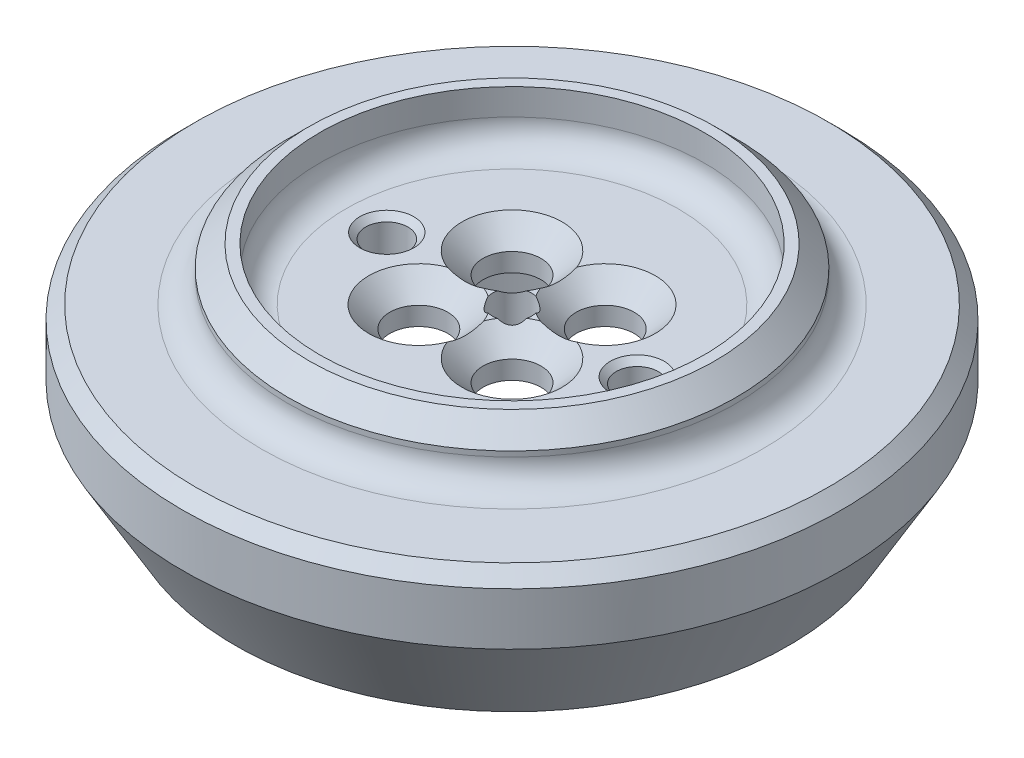
SolidWorks part; units mm, degrees
material "Brass"
ref_plane "Front Plane" through (0, 0, 0) normal (0, 0, 1) x (1, 0, 0)
ref_plane "Top Plane" through (0, 0, 0) normal (0, 1, 0) x (1, 0, 0)
ref_plane "Right Plane" through (0, 0, 0) normal (1, 0, 0) x (0, 0, -1)
sketch "Sketch1" plane through (0, 0, 0) normal (0, 1, 0) x (1, 0, 0)
  circle A0 centre (0, 0) radius 12.5
  dimension "D1" = 25
extrude "Boss-Extrude1" add sketch "Sketch1" along normal blind 1.5
sketch "Sketch2" plane through (0, 1.5, 0) normal (0, 1, 0) x (1, 0, 0)
  circle A0 centre (0, 0) radius 0.75
  dimension "D1" = 1.5
extrude "Cut-Extrude1" cut sketch "Sketch2" against normal through all both and the other way through all
hole_wizard "CSK for M2 Flat Head Machine Screw1" positions "Sketch3" profile "Sketch4" countersink size "M2" standard "ANSI Metric"
sketch "Sketch3" plane through (0, 1.5, 0) normal (0, 1, 0) x (1, 0, 0)
  line L1 (-1.7678, 1.7678) -> (1.7678, 1.7678)
  line L2 (-1.7678, 1.7678) -> (-1.7678, -1.7678)
  line L3 (-1.7678, -1.7678) -> (1.7678, -1.7678)
  line L4 (1.7678, 1.7678) -> (1.7678, -1.7678)
  line L5 (-1.7678, 1.7678) -> (1.7678, -1.7678) construction
  point P0 (-1.7678, 1.7678)
  point P2 (1.7678, 1.7678)
  point P4 (1.7678, -1.7678)
  point P6 (-1.7678, -1.7678)
  point P120 (0, 0)
  dimension "D1" = 5
sketch "Sketch4" plane through (-1.7678, 1.5, -1.7678) normal (1, 0, 0) x (0, 0, 1)
  line L0 (0, 0) -> (0, 5.6609)
  line L1 (0, 5.6609) -> (1.1, 5)
  line L2 (1.1, 5) -> (1.1, 0.8)
  line L3 (1.1, 0.8) -> (1.9, 0)
  line L5 (1.9, 0) -> (0, 0)
  line L6 (-1.1, 0.8) -> (-1.9, 0) construction
  line L10 (0, 5.6609) -> (-1.1, 5) construction
  line L11 (0, -6.35) -> (0, 107.95) construction
  dimension "Hole Dia." = 2.2
  dimension "Hole Depth" = 5
  dimension "Near C'Sink Dia." = 3.8
  dimension "Near C'Sink Angle" = 90
  dimension "Drill Angle" = 118
sketch "Sketch6" plane through (0, 0, 0) normal (0, 0, 1) x (1, 0, 0)
  line L0 (-12.5, 0) -> (-12.5, -1.15)
  line L1 (-12.5, -1.15) -> (-7.05, -1.15)
  line L2 (-7.05, -1.15) -> (-5, 0)
  line L3 (-5, 0) -> (-12.5, 0)
  line L4 (0, 0) -> (0, -5.6432) construction
  dimension "D1" = 1.15
  dimension "D2" = 5
  dimension "D3" = 7.05
revolve "Revolve1" add sketch "Sketch6" angle 360 about L4
sketch "Sketch7" plane through (0, -1.15, 0) normal (0, -1, 0) x (1, 0, 0)
  circle A0 centre (0, 0) radius 7.05 construction
  circle A1 centre (0, 0) radius 12.5
  circle A2 centre (0, 0) radius 12.5
  circle A3 centre (0, 0) radius 7.05
  dimension "D1" = 0
extrude "Boss-Extrude2" add sketch "Sketch7" along normal blind 3.3
sketch "Sketch11" plane through (0, 1.5, 0) normal (0, 1, 0) x (1, 0, 0)
  line L0 (0, 0) -> (-3.2481, 0) construction
  line L1 (-7.25, 5.1678) -> (-7.25, -5.1678)
  line L2 (-7.25, -5.1678) -> (7.25, -5.1678)
  line L3 (7.25, -5.1678) -> (7.25, 5.1678)
  line L4 (7.25, 5.1678) -> (-7.25, 5.1678)
  line L5 (-7.25, 5.1678) -> (7.25, -5.1678) construction
  line L6 (-1.7678, -3.6678) -> (-1.7678, -5.1678) construction
  line L7 (-0.6889, -3.6678) -> (-2.8466, -3.6678) construction
  circle A0 centre (0, 0) radius 10
  arc A4 (-2.4642, 0) -> (0, -2.4642) centre (-1.7678, -1.7678) ccw construction
  dimension "D1" = 1.5
  dimension "D3" = 20
  dimension "D2" = 14.5
extrude "Boss-Extrude3" [suppressed] add sketch "Sketch11" along normal blind 3
fillet "Fillet2" [suppressed] radius 5
fillet "Fillet3" [suppressed] radius 1
sketch "Sketch15" plane through (0, 1.5, 0) normal (0, 1, 0) x (1, 0, 0)
  circle A0 centre (0, 0) radius 7.3
  circle A1 centre (0, 0) radius 8.5
  dimension "D1" = 14.6
  dimension "D2" = 17
extrude "Boss-Extrude4" add sketch "Sketch15" along normal blind 2
fillet "Fillet1" radius 1 4 edges at (0, 0, 5) (0, -1.15, 7.05) (0, 1.5, 7.3) (0, 1.5, 8.5)
loft "Loft2" [suppressed] add
sketch "Sketch14" [suppressed] plane through (0, 4.5, 0) normal (0, 1, 0) x (1, 0, 0)
  circle A0 centre (0, 0) radius 10 construction
  circle A1 centre (0, 0) radius 10
extrude "Cut-Extrude2" [suppressed] cut sketch "Sketch14" against normal through all both and the other way through all
combine bodies "Combine1" [suppressed] operation type add bodies to combine 110 107
chamfer "Chamfer1" distance 0.5 angle 45 1 edges at (0, 1.5, 12.5)
chamfer "Chamfer2" distance 1 angle 45 1 edges at (0, -4.45, -7.05)
chamfer "Chamfer3" distance 2 angle 60 1 edges at (0, -4.45, -12.5) first distance on face at (0, -4.45, -8.05)
hole_wizard "M2x0.4 Tapped Hole1" positions "Sketch8" profile "Sketch9" tap size "M2x0.4" standard "ANSI Metric"
sketch "Sketch8" plane through (0, 1.5, 0) normal (0, 1, 0) x (1, 0, 0)
  line L0 (-4.75, 0) -> (4.75, 0) construction
  point P0 (-4.75, 0)
  point P2 (4.75, 0)
  dimension "D1" = 9.5
sketch "Sketch9" plane through (-4.75, 1.5, 0) normal (1, 0, 0) x (0, 0, 1)
  line L0 (0, 0) -> (0, 5.6807)
  line L1 (0, 5.6807) -> (0.8, 5.2)
  line L2 (0.8, 5.2) -> (0.8, 0.225)
  line L3 (0.8, 0.225) -> (1.025, 0)
  line L5 (1.025, 0) -> (0, 0)
  line L6 (-0.8, 0.225) -> (-1.025, 0) construction
  line L10 (0, 5.6807) -> (-0.8, 5.2) construction
  line L11 (0, -6.35) -> (0, 107.95) construction
  dimension "Tap Drill Dia." = 1.6
  dimension "Tap Drill Depth" = 5.2
  dimension "Near C'Sink Dia." = 2.05
  dimension "Near C'Sink Angle" = 90
  dimension "Drill Angle" = 118
cosmetic thread "Hole Thread1" parameters "D1"=2.4801, "D2"=2
cosmetic thread "Hole Thread2" parameters "D1"=2.4801, "D2"=2
chamfer "Chamfer4" distance 0.8 angle 45 1 edges at (0, 3.5, 8.5)
